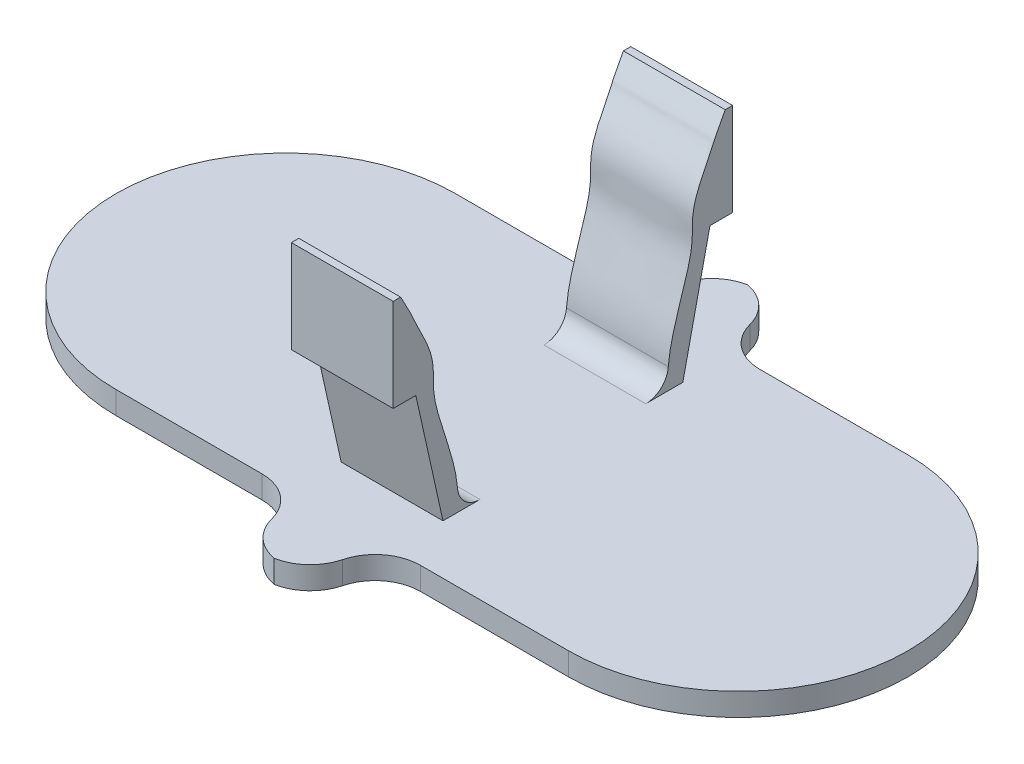
SolidWorks part; units mm, degrees
ref_plane "Front Plane" through (0, 0, 0) normal (0, 0, 1) x (1, 0, 0)
ref_plane "Top Plane" through (0, 0, 0) normal (0, 1, 0) x (1, 0, 0)
ref_plane "Right Plane" through (0, 0, 0) normal (1, 0, 0) x (0, 0, -1)
sketch "Sketch1" plane through (0, 0, 0) normal (0, 1, 0) x (1, 0, 0)
  line L0 (0, 0) -> (25.4, 0) construction
  line L1 (0, 9.525) -> (25.4, 9.525)
  line L2 (0, -9.525) -> (25.4, -9.525)
  arc A0 (0, 9.525) -> (0, -9.525) centre (0, 0) ccw
  arc A1 (25.4, -9.525) -> (25.4, 9.525) centre (25.4, 0) ccw
  point P3 (12.7, 0)
  dimension "D1" = 19.05
  dimension "D2" = 25.4
extrude "Boss-Extrude1" add sketch "Sketch1" along normal blind 1.27
sketch "Sketch2" plane through (0, 1.27, 0) normal (0, 1, 0) x (1, 0, 0)
  line L0 (12.7, 9.525) -> (12.7, -9.525) construction
  line L1 (25.4, 9.525) -> (0, 9.525) construction
  line L2 (0, -9.525) -> (25.4, -9.525) construction
  line L3 (0, 0) -> (25.4, 0) construction
  line L4 (9.8425, -9.525) -> (9.8425, -5.715)
  line L5 (9.8425, -5.715) -> (15.5575, -5.715)
  line L6 (15.5575, -5.715) -> (15.5575, -9.525)
  line L7 (15.5575, -9.525) -> (9.8425, -9.525)
  point P12 (12.7, -9.525)
  dimension "D1" = 5.715
  dimension "D2" = 3.81
extrude "Boss-Extrude2" add sketch "Sketch2" along normal blind 12.065
sketch "Sketch3" plane through (9.8425, 0, 0) normal (-1, 0, 0) x (0, 0, 1)
  line L0 (5.715, 13.335) -> (9.525, 13.335) construction
  line L1 (5.715, 1.27) -> (9.525, 1.27) construction
  line L2 (9.1092, 13.335) -> (5.715, 13.335)
  line L3 (5.715, 13.335) -> (5.715, 1.27)
  line L4 (5.715, 1.27) -> (5.969, 1.27)
  line L5 (9.525, 1.27) -> (9.525, 8.128)
  line L6 (9.525, 13.335) -> (9.525, 1.27) construction
  line L7 (9.525, 8.128) -> (8.255, 8.128)
  line L8 (8.255, 8.128) -> (6.731, 1.27)
  line L9 (6.731, 1.27) -> (9.525, 1.27)
  spline S0 degree 3 poles (5.969, 1.27) (5.5493, 3.3504) (7.7845, 7.2506) (7.0734, 9.2875) (8.9524, 12.9691) (8.0558, 11.368) (9.1092, 13.335) knots 0 0 0 0 0.483316 0.688146 0.724664 1 1 1 1
  point P15 (6.981, 5.2774)
  point P18 (6.1143, 3.6338)
  point P19 (7.6498, 7.8982)
  point P20 (7.2533, 7.8592)
  point P21 (0, 0)
  point P26 (0, 0)
  dimension "D1" = 0.254
  dimension "D2" = 0.762
  dimension "D3" = 1.27
  dimension "D4" = 6.858
extrude "Cut-Extrude1" cut sketch "Sketch3" against normal up to next
mirror "Mirror1" about plane through (0, 0, 0) normal (0, 0, 1) of "Boss-Extrude2", "Cut-Extrude1"
sketch "Sketch5" plane through (0, 0, 9.525) normal (0, 0, 1) x (1, 0, 0)
  line L0 (0, 0) -> (25.4, 0) construction
  line L1 (10.7347, 1.27) -> (14.5447, 1.27)
  line L2 (10.7347, 1.27) -> (10.7347, 0)
  line L3 (10.7347, 0) -> (14.5447, 0)
  line L4 (14.5447, 1.27) -> (14.5447, 0)
  line L5 (10.7347, 1.27) -> (14.5447, 0) construction
  line L6 (10.7347, 0) -> (14.5447, 1.27) construction
  line L7 (15.5575, 1.27) -> (9.8425, 1.27) construction
  point P0 (12.6397, 0.635)
  dimension "D1" = 3.81
extrude "Boss-Extrude3" add sketch "Sketch5" along normal blind 3.81
fillet "Fillet1" radius 1.27 2 edges at (12.7, 1.27, 5.969) (12.7, 1.27, -5.969)
mirror "Mirror4" about plane through (0, 0, 0) normal (0, 0, 1) of "Boss-Extrude3"
fillet "Fillet2" radius 2.54 4 edges at (14.5447, 0.635, 9.525) (10.7347, 0.635, 9.525) (14.5447, 0.635, -9.525) (10.7347, 0.635, -9.525)
fillet "Fillet3" radius 2.54 4 edges at (14.5447, 0.635, 13.335) (10.7347, 0.635, 13.335) (14.5447, 0.635, -13.335) (10.7347, 0.635, -13.335)
